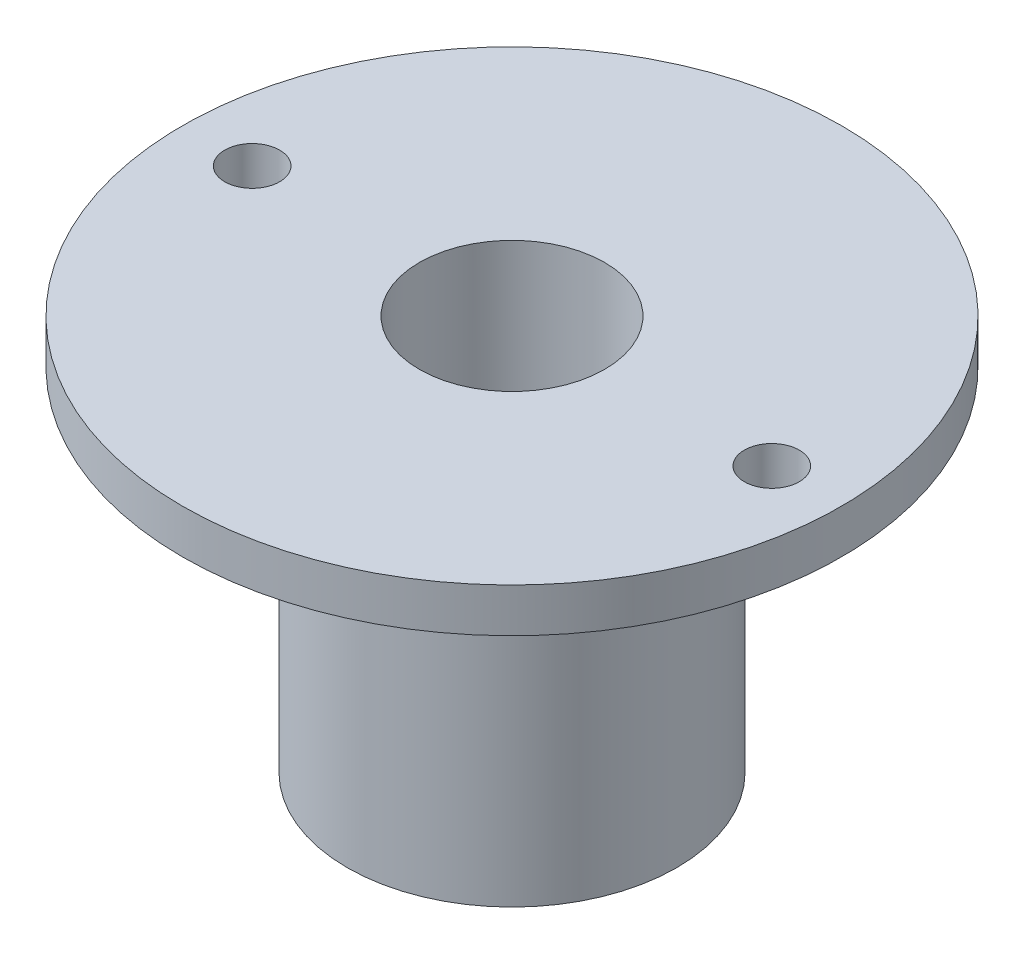
SolidWorks part; units mm, degrees
ref_plane "Front Plane" through (0, 0, 0) normal (0, 0, 1) x (1, 0, 0)
ref_plane "Top Plane" through (0, 0, 0) normal (0, 1, 0) x (1, 0, 0)
ref_plane "Right Plane" through (0, 0, 0) normal (1, 0, 0) x (0, 0, -1)
sketch "Sketch1" plane through (0, 0, 0) normal (0, 1, 0) x (1, 0, 0)
  circle A0 centre (0, 0) radius 15
  dimension "D1" = 30
extrude "Boss-Extrude1" add sketch "Sketch1" against normal blind 2
sketch "Sketch2" plane through (0, -2, 0) normal (0, -1, 0) x (1, 0, 0)
  circle A0 centre (0, 0) radius 7.5
  dimension "D1" = 15
extrude "Boss-Extrude2" add sketch "Sketch2" along normal blind 16
hole_wizard "3/8-24 Tapped Hole1" positions "Sketch4" profile "Sketch3" tap size "3/8-24" standard "ANSI Inch"
sketch "Sketch4" plane through (0, -18, 0) normal (0, -1, 0) x (-1, 0, 0)
  point P0 (0, 0)
sketch "Sketch3" plane through (0, -18, 0) normal (1, 0, 0) x (0, 0, -1)
  line L0 (0, 0) -> (0, 26.9335)
  line L1 (0, 26.9335) -> (4.2164, 24.4)
  line L2 (4.2164, 24.4) -> (4.2164, 0)
  line L5 (4.2164, 0) -> (0, 0)
  line L10 (0, 26.9335) -> (-4.2164, 24.4) construction
  line L11 (0, -6.35) -> (0, 107.95) construction
  dimension "Tap Drill Dia." = 8.4328
  dimension "Tap Drill Depth" = 24.4
  dimension "Drill Angle" = 118
cosmetic thread "Hole Thread1" parameters "D1"=18, "D2"=9.525
sketch "Sketch5" plane through (0, 0, 0) normal (0, 1, 0) x (1, 0, 0)
  line L0 (11.825, 0) -> (-11.825, 0) construction
  circle A0 centre (11.825, 0) radius 1.25
  circle A1 centre (-11.825, 0) radius 1.25
  point P9 (0, 0)
  dimension "D2" = 2.5
  dimension "D1" = 23.65
extrude "Cut-Extrude1" cut sketch "Sketch5" against normal blind 10
